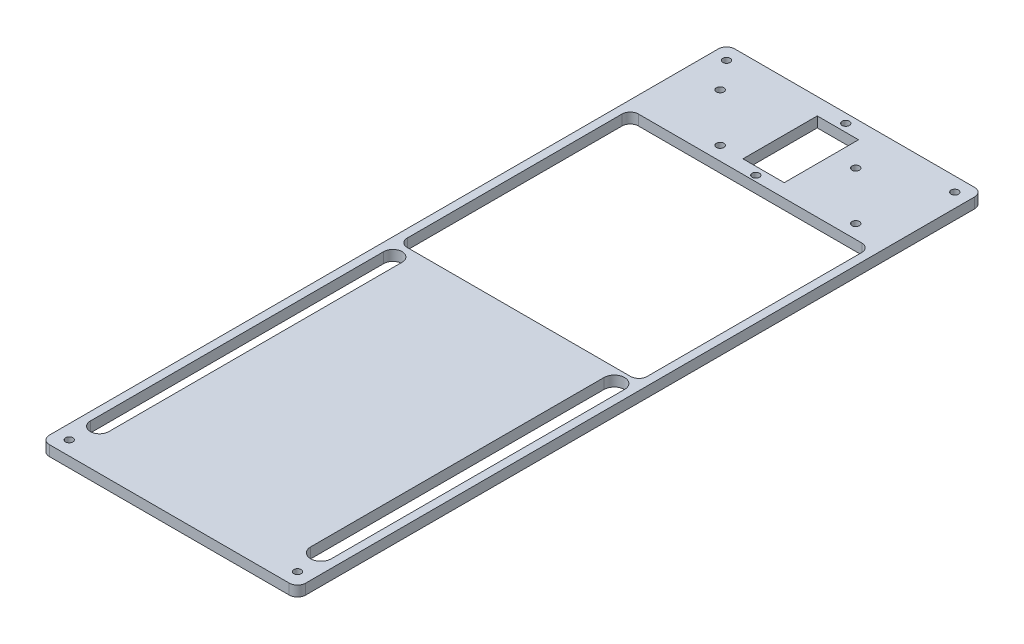
SolidWorks part; units mm, degrees
material "Brass"
ref_plane "Front Plane" through (0, 0, 0) normal (0, 0, 1) x (1, 0, 0)
ref_plane "Top Plane" through (0, 0, 0) normal (0, 1, 0) x (1, 0, 0)
ref_plane "Right Plane" through (0, 0, 0) normal (1, 0, 0) x (0, 0, -1)
sketch "Sketch2" plane through (0, 0, 0) normal (0, 0, 1) x (1, 0, 0)
  line L0 (-44.45, 0) -> (-44.45, -3.2004)
  line L1 (0, 0) -> (0, -3.2004) construction
  line L2 (-44.45, -3.2004) -> (34.3945, -3.2004)
  line L3 (34.3945, 0) -> (34.3945, -3.2004)
  line L4 (-44.45, 0) -> (34.3945, 0)
  dimension "D1" = 78.8445
  dimension "D2" = 3.2004
extrude "Boss-Extrude1" add sketch "Sketch2" along normal blind 210.82 contours L4 L3 L2 L0
sketch "Sketch3" plane through (0, -3.2004, 0) normal (0, -1, 0) x (1, 0, 0)
  line L0 (-39.0762, 103.2783) -> (-39.0762, 107.9974) construction
  line L1 (30.0765, 210.82) -> (30.0765, 206.502) construction
  line L2 (30.0765, 206.502) -> (34.3945, 206.502) construction
  line L3 (-44.45, 210.82) -> (34.3945, 210.82) construction
  line L4 (-5.0278, 57.15) -> (-5.0278, 0) construction
  line L5 (-44.45, 0) -> (34.3945, 0) construction
  line L6 (-41.91, 107.9974) -> (-36.2424, 107.9974) construction
  line L7 (-41.91, 107.9974) -> (-41.91, 198.224)
  line L8 (-41.91, 198.224) -> (-36.2424, 198.224) construction
  line L9 (-36.2424, 107.9974) -> (-36.2424, 198.224)
  line L10 (-39.0762, 210.82) -> (-39.0762, 201.0579) construction
  line L11 (-41.91, 153.1107) -> (-44.45, 153.1107) construction
  line L12 (25.5045, 107.6562) -> (31.8545, 107.6562) construction
  line L13 (25.5045, 107.6562) -> (25.5045, 197.8829)
  line L14 (25.5045, 197.8829) -> (31.8545, 197.8829) construction
  line L15 (31.8545, 107.6562) -> (31.8545, 197.8829)
  line L16 (28.6795, 210.82) -> (28.6795, 201.0579) construction
  line L17 (34.3945, 152.7696) -> (31.8545, 152.7696) construction
  line L18 (34.3945, 210.82) -> (34.3945, 0) construction
  line L19 (-44.45, 4.318) -> (-40.132, 4.318) construction
  line L20 (34.3945, 210.82) -> (34.3945, 0) construction
  line L21 (-44.45, 210.82) -> (-44.45, 0) construction
  line L22 (-44.45, 210.82) -> (-44.45, 0) construction
  line L23 (-40.132, 210.82) -> (-40.132, 206.502) construction
  line L24 (-44.45, 206.502) -> (-40.132, 206.502) construction
  line L25 (-44.45, 210.82) -> (34.3945, 210.82) construction
  line L26 (-40.132, 4.318) -> (-40.132, 0) construction
  line L27 (-44.45, 0) -> (34.3945, 0) construction
  line L28 (34.3945, 4.318) -> (30.0765, 4.318) construction
  line L29 (30.0765, 0) -> (30.0765, 4.318) construction
  line L30 (-11.3778, 28.0256) -> (-11.3778, 5.1656)
  line L31 (1.3222, 28.0256) -> (1.3222, 5.1656)
  line L32 (-11.3778, 5.1656) -> (1.3222, 5.1656)
  line L33 (-11.3778, 28.0256) -> (1.3222, 28.0256)
  line L34 (-18.4797, 27.94) -> (-33.2664, 13.1534) construction
  line L35 (23.2109, 27.94) -> (8.4242, 13.1534) construction
  line L36 (-44.45, 0) -> (34.3945, 0) construction
  line L37 (-33.2664, 13.1534) -> (-44.45, 13.1534) construction
  line L39 (34.3945, 27.94) -> (23.2109, 27.94) construction
  line L40 (23.2109, 27.94) -> (23.2109, 0) construction
  line L41 (23.2109, 27.94) -> (-18.4797, 27.94) construction
  line L42 (31.8545, 32.1583) -> (-41.91, 32.1583)
  line L43 (31.8545, 32.1583) -> (31.8545, 103.2783)
  line L44 (31.8545, 103.2783) -> (-41.91, 103.2783)
  line L45 (-41.91, 32.1583) -> (-41.91, 103.2783)
  arc A1 (-41.91, 198.224) -> (-36.2424, 198.224) centre (-39.0762, 198.224) cw
  arc A2 (-36.2424, 107.9974) -> (-41.91, 107.9974) centre (-39.0762, 107.9974) cw
  arc A3 (25.5045, 197.8829) -> (31.8545, 197.8829) centre (28.6795, 197.8829) cw
  arc A4 (31.8545, 107.6562) -> (25.5045, 107.6562) centre (28.6795, 107.6562) cw
  circle A5 centre (-40.132, 206.502) radius 1.1303
  circle A6 centre (30.0765, 206.502) radius 1.1303
  circle A7 centre (-40.132, 4.318) radius 1.1303
  circle A8 centre (30.0765, 4.318) radius 1.1303
  circle A9 centre (-5.0278, 30.4259) radius 1.1303
  circle A10 centre (-5.0278, 2.7653) radius 1.1303
  circle A11 centre (23.2109, 27.94) radius 1.143
  circle A12 centre (8.4242, 13.1534) radius 1.143
  circle A13 centre (-18.4797, 27.94) radius 1.143
  circle A14 centre (-33.2664, 13.1534) radius 1.143
  point P53 (-5.0278, 28.0256)
  point P58 (-5.0278, 28.0256)
  point P67 (-5.0278, 5.1656)
  dimension "D11" = 2.2606
  dimension "D15" = 2.2606
  dimension "D16" = 2.7653
  dimension "D18" = 2.4003
  dimension "D19" = 45
  dimension "D21" = 4.7191
  dimension "D25" = 2.286
  dimension "D2" = 57.15
  dimension "D3" = 71.12
  dimension "D4" = 5.6676
  dimension "D5" = 9.7621
  dimension "D6" = 2.54
  dimension "D7" = 90.2266
  dimension "D8" = 6.35
  dimension "D9" = 9.7621
  dimension "D10" = 2.54
  dimension "D12" = 4.318
  dimension "D13" = 22.86
  dimension "D14" = 12.7
  dimension "D17" = 2.4003
  dimension "D20" = 11.1836
  dimension "D23" = 27.94
  dimension "D26" = 11.1836
  dimension "D27" = 20.9115
extrude "Cut-Extrude1" cut sketch "Sketch3" against normal through all
fillet "Fillet1" radius 2.54 4 edges at (34.3945, -1.6002, 210.82) (-44.45, -1.6002, 210.82) (-44.45, -1.6002, 0) (34.3945, -1.6002, 0)
fillet "Fillet2" radius 2.54 4 edges at (31.8545, -1.6002, 103.2783) (-41.91, -1.6002, 103.2783) (-41.91, -1.6002, 32.1583) (31.8545, -1.6002, 32.1583)
sketch "Sketch4" plane through (0, 0, 210.82) normal (0, 0, 1) x (1, 0, 0)
  line L0 (-5.0278, 0) -> (-5.0278, -3.2004) construction
  line L1 (-44.45, 0) -> (34.3945, 0) construction
  line L2 (-44.45, -3.2004) -> (34.3945, -3.2004) construction
sketch "Sketch6" plane through (34.3945, 0, 0) normal (1, 0, 0) x (0, 0, -1)
  line L0 (-105.41, 0) -> (-105.41, -3.2004) construction
  line L3 (-210.82, -3.2004) -> (0, -3.2004) construction
  line L4 (-210.82, 0) -> (0, 0) construction
